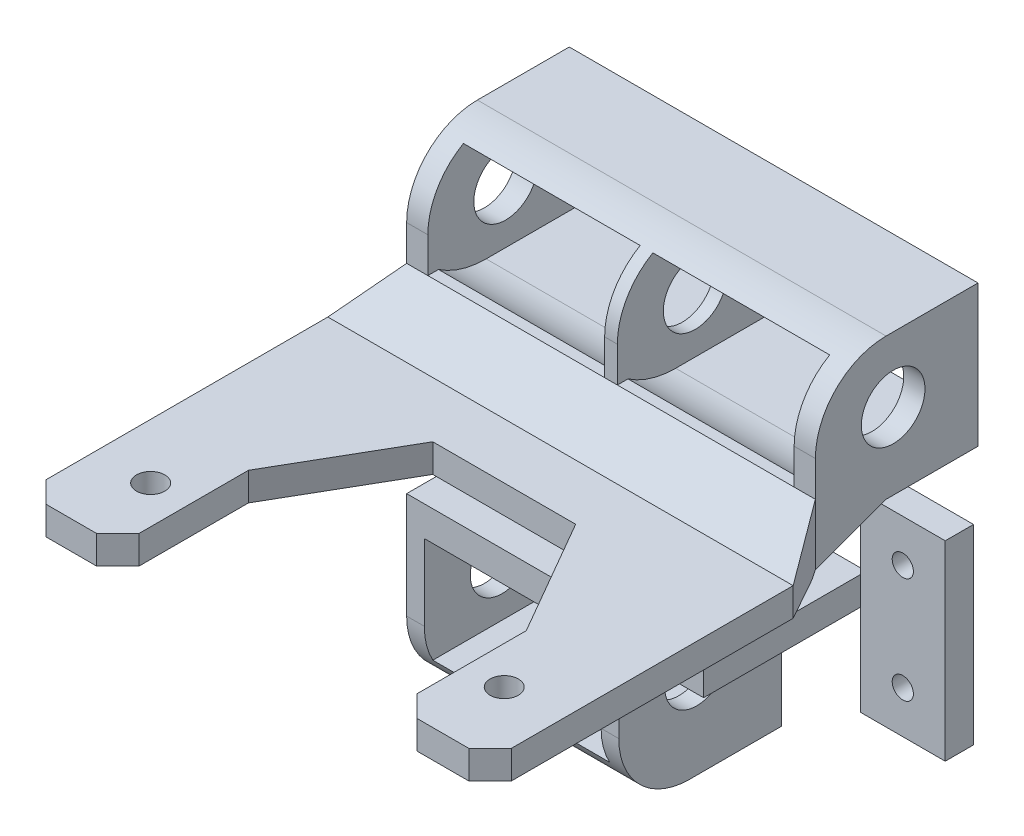
SolidWorks part; units mm, degrees
ref_plane "Alzado" through (0, 0, 0) normal (0, 0, 1) x (1, 0, 0)
ref_plane "Planta" through (0, 0, 0) normal (0, 1, 0) x (1, 0, 0)
ref_plane "Vista lateral" through (0, 0, 0) normal (1, 0, 0) x (0, 0, -1)
sketch "Croquis2" plane through (0, 0, 0) normal (0, 0, 1) x (1, 0, 0)
  line L0 (30, 41) -> (57.8, 41)
  line L1 (0, 0) -> (30, 0)
  line L2 (0, 0) -> (0, 66.2)
  line L3 (-22.2756, 55.1) -> (45.3117, 55.1) construction
  line L4 (30, 0) -> (30, 41)
  line L7 (0, 66.2) -> (57.8, 66.2)
  line L8 (57.8, 41) -> (57.8, 66.2)
  line L9 (-13, 9.1) -> (37, 9.1) construction
  dimension "D1" = 30
  dimension "D2" = 57.8
  dimension "D5" = 11.1
  dimension "D6" = 46
  dimension "D7" = 9.1
extrude "Saliente-Extruir3" add sketch "Croquis2" along normal blind 3
sketch "Croquis6" plane through (0, 0, 3) normal (0, 0, 1) x (1, 0, 0)
  line L0 (30, 0) -> (30, 41) construction
  line L1 (0, 0) -> (30, 0)
  line L2 (0, 0) -> (0, 20)
  line L3 (0, 20) -> (30, 20)
  line L4 (30, 0) -> (30, 20)
  line L5 (0, 66.2) -> (0, 0) construction
  line L6 (57.8, 41) -> (57.8, 66.2) construction
  line L7 (0, 66.2) -> (57.8, 66.2)
  line L8 (0, 66.2) -> (0, 46.2)
  line L9 (0, 46.2) -> (57.8, 46.2)
  line L10 (57.8, 66.2) -> (57.8, 46.2)
  dimension "D1" = 20
  dimension "D2" = 20
extrude "Saliente-Extruir4" add sketch "Croquis6" along normal blind 20
sketch "Croquis22" plane through (0, 0, 23) normal (0, 0, 1) x (1, 0, 0)
  line L1 (61.8, 42.2) -> (-4, 42.2)
  line L2 (61.8, 42.2) -> (61.8, 51.2)
  line L3 (61.8, 51.2) -> (-4, 51.2)
  line L4 (-4, 42.2) -> (-4, 51.2)
  line L6 (0, 46.2) -> (57.8, 46.2) construction
  line L7 (0, 66.2) -> (0, 46.2) construction
  line L8 (57.8, 46.2) -> (57.8, 66.2) construction
  dimension "D1" = 9
  dimension "D2" = 5
  dimension "D3" = 4
  dimension "D4" = 4
extrude "Saliente-Extruir9" add sketch "Croquis22" along normal blind 50 and the other way blind 10
sketch "Croquis9" plane through (57.8, 0, 0) normal (1, 0, 0) x (0, 0, -1)
  line L1 (0, 41) -> (0, 66.2) construction
  line L2 (-23, 0) -> (0, 0) construction
  line L3 (0, 0) -> (0, 41) construction
  circle A0 centre (-12, 57) radius 4.5
  circle A1 centre (-12, 11) radius 4.5
  dimension "D1" = 9
  dimension "D2" = 9
  dimension "D3" = 46
  dimension "D4" = 12
  dimension "D5" = 11
  dimension "D6" = 12
extrude "Cortar-Extruir1" cut sketch "Croquis9" against normal through all
sketch "Croquis17" plane through (0, 0, 23) normal (0, 0, 1) x (1, 0, 0)
  line L0 (30, 6.5) -> (30, 15.5) construction
  line L3 (30, 6.5) -> (30, 15.5) construction
  line L4 (2.5, 3.25) -> (27.5, 3.25)
  line L5 (2.5, 3.25) -> (2.5, 18.75)
  line L6 (2.5, 18.75) -> (27.5, 18.75)
  line L7 (27.5, 3.25) -> (27.5, 18.75)
  line L8 (2.5, 3.25) -> (27.5, 18.75) construction
  line L9 (2.5, 18.75) -> (27.5, 3.25) construction
  line L10 (30, 11) -> (0, 11) construction
  line L11 (0, 20) -> (0, 0) construction
  point P6 (15, 11)
  dimension "D1" = 15.5
  dimension "D2" = 25
extrude "Cortar-Extruir6" cut sketch "Croquis17" against normal up to surface (23 mm away) up to face at (29.2667, 35.7333, 0)
sketch "Croquis18" plane through (0, 0, 23) normal (0, 0, 1) x (1, 0, 0)
  line L0 (-13.9, 57) -> (43.9, 57) construction
  line L1 (0, 66.2) -> (0, 51.2) construction
  line L2 (57.8, 51.2) -> (57.8, 66.2) construction
  line L3 (0, 57) -> (57.8, 57) construction
  line L4 (3, 49.125) -> (28, 49.125)
  line L5 (3, 49.125) -> (3, 64.875)
  line L6 (3, 64.875) -> (28, 64.875)
  line L7 (28, 49.125) -> (28, 64.875)
  line L8 (3, 49.125) -> (28, 64.875) construction
  line L9 (3, 64.875) -> (28, 49.125) construction
  line L10 (54.8, 49.125) -> (29.8, 49.125)
  line L11 (54.8, 49.125) -> (54.8, 64.875)
  line L12 (54.8, 64.875) -> (29.8, 64.875)
  line L13 (29.8, 49.125) -> (29.8, 64.875)
  line L14 (54.8, 49.125) -> (29.8, 64.875) construction
  line L15 (54.8, 64.875) -> (29.8, 49.125) construction
  point P6 (15.5, 57)
  point P11 (42.3, 57)
  dimension "D1" = 15.75
  dimension "D2" = 25
  dimension "D3" = 3
  dimension "D4" = 3
extrude "Cortar-Extruir7" cut sketch "Croquis18" against normal up to surface (23 mm away) up to face at (15, 11, 0)
sketch "Croquis12" plane through (0, 20, 0) normal (0, 1, 0) x (1, 0, 0)
  line L1 (30, 0) -> (30, -3)
  line L2 (42, 0) -> (42, -23)
  line L3 (42, -23) -> (0, -23)
  line L4 (0, -3) -> (0, -23)
  line L5 (30, -23) -> (0, -23) construction
  line L6 (30, -23) -> (30, -3) construction
  line L8 (0, -23) -> (0, -3) construction
  line L9 (30, -3) -> (0, -3)
  line L10 (42, 0) -> (30, 0)
  line L11 (30, -23) -> (42, -23)
  line L12 (30, -3) -> (0, -3) construction
  circle A0 centre (36, -19) radius 1.5
  circle A1 centre (36, -4) radius 1.5
  dimension "D3" = 4
  dimension "D5" = 3
  dimension "D6" = 3
  dimension "D10" = 6
  dimension "D1" = 12
  dimension "D2" = 15
sketch "Croquis14" plane through (0, 66.2, 0) normal (0, 1, 0) x (1, 0, 0)
  line L1 (57.8, -23) -> (57.8, 0) construction
  line L2 (61.8, -73) -> (-4, -73) construction
  line L3 (9.1566, -54.5253) -> (9.1566, -73)
  line L4 (18.6964, -38.0018) -> (9.1566, -54.5253)
  line L8 (48.4434, -54.5253) -> (38.9036, -38.0018)
  line L9 (38.9036, -38.0018) -> (18.6964, -38.0018)
  line L10 (61.8, -73) -> (-4, -73) construction
  line L11 (9.1566, -73) -> (48.4434, -73)
  line L12 (48.4434, -73) -> (48.4434, -54.5253)
  line L14 (19.7861, -73.0018) -> (29.8898, -73.0018) [skipped]
  line L15 (13.6446, -64.2518) -> (16.6756, -69.5018) [skipped]
  line L16 (39.9524, -71.1852) -> (42.9835, -65.9352) [skipped]
  arc A0 (29.0535, -73) -> (28.5465, -73) centre (28.8, -55.5018) ccw construction
  circle A1 centre (3.8, -63) radius 2
  circle A2 centre (53.8, -63) radius 2
  dimension "D3" = 4
  dimension "D4" = 4
  dimension "D5" = 35
  dimension "D6" = 10
  dimension "D7" = 4
  dimension "D2" = 25
  dimension "D1" = 50
extrude "Cortar-Extruir4" cut sketch "Croquis14" against normal through all
sketch "Croquis16" plane through (30, 0, 0) normal (1, 0, 0) x (0, 0, -1)
  line L0 (-2.25, 36.0874) -> (-6, 36.0874)
  line L1 (-2.25, 40.0874) -> (-6, 40.0874)
  line L2 (-2.25, 40.0874) -> (-2.25, 38.0874)
  line L3 (-2.25, 38.0874) -> (-6, 38.0874)
  line L4 (-6, 40.0874) -> (-6, 38.0874)
  line L5 (-2.25, 36.0874) -> (-2.25, 34.0874)
  line L6 (-2.25, 34.0874) -> (-6, 34.0874)
  line L7 (-6, 36.0874) -> (-6, 34.0874)
  line L8 (-2.25, 32.0874) -> (-6, 32.0874)
  line L9 (-2.25, 32.0874) -> (-2.25, 30.0874)
  line L10 (-2.25, 30.0874) -> (-6, 30.0874)
  line L11 (-6, 32.0874) -> (-6, 30.0874)
  line L12 (-2.25, 28.0874) -> (-6, 28.0874)
  line L13 (-2.25, 28.0874) -> (-2.25, 26.0874)
  line L14 (-2.25, 26.0874) -> (-6, 26.0874)
  line L15 (-6, 28.0874) -> (-6, 26.0874)
  line L16 (-3, 20) -> (-3, 41) construction
  dimension "D1" = 2
  dimension "D2" = 2
  dimension "D3" = 2
  dimension "D4" = 2
  dimension "D5" = 2
  dimension "D6" = 2
  dimension "D7" = 2
  dimension "D8" = 0.75
extrude "Cortar-Extruir5" cut sketch "Croquis16" against normal through all
sketch "Croquis23" plane through (3, 0, 0) normal (1, 0, 0) x (0, 0, -1)
  line L0 (-23, 49.125) -> (-14.755, 49.125)
  line L1 (-23, 49.125) -> (-23, 51.2)
  line L2 (-23, 51.2) -> (-21.5, 51.2)
  arc A0 (-21.5, 51.2) -> (-14.755, 49.125) centre (-14.755, 61.125) ccw
  dimension "D1" = 12
  dimension "D2" = 1.5
extrude "Saliente-Extruir10" add sketch "Croquis23" along normal up to surface (51.8 mm away) up to face at (54.8, 55.84, 13.8)
sketch "Croquis24" plane through (0, 0, 3) normal (0, 0, 1) x (1, 0, 0)
  line L0 (0, 38.0874) -> (0, 36.0874) construction
  line L1 (0, 41) -> (-13.9, 41)
  line L2 (0, 41) -> (0, 46.2)
  line L3 (0, 46.2) -> (-13.9, 46.2)
  line L4 (-13.9, 41) -> (-13.9, 46.2)
  line L5 (30, 41) -> (57.8, 41)
  line L6 (30, 41) -> (30, 46.2)
  line L7 (30, 46.2) -> (57.8, 46.2)
  line L8 (57.8, 41) -> (57.8, 46.2)
  line L9 (30, 36.0874) -> (30, 38.0874) construction
extrude "Cortar-Extruir9" cut sketch "Croquis24" against normal through all
fillet "Redondeo1" radius 10 1 edges at (28.9, 66.2, 23)
sketch "Croquis28" plane through (30, 0, 0) normal (1, 0, 0) x (0, 0, -1)
  line L0 (-9, 46.2) -> (-3, 40.2)
  line L1 (-13, 46.2) -> (0, 46.2) construction
  line L2 (-3, 40.0874) -> (-3, 46.2) construction
  line L3 (-3, 40.2) -> (-3, 46.2)
  line L4 (-3, 46.2) -> (-9, 46.2)
  line L5 (-3, 26) -> (-6, 23)
  line L6 (-3, 20) -> (-3, 26.0874) construction
  line L8 (-6, 23) -> (-3, 23)
  line L9 (-3, 23) -> (-3, 26)
  dimension "D1" = 6
  dimension "D2" = 6
  dimension "D3" = 3
  dimension "D4" = 3
extrude "Saliente-Extruir12" add sketch "Croquis28" against normal up to surface (30 mm away) up to face at (0, 57, 7.5)
sketch "Croquis29" plane through (0, 0, 0) normal (0, -1, 0) x (1, 0, 0)
  line L4 (0, 0) -> (30, 0)
  line L5 (30, 0) -> (30, 23)
  line L6 (30, 23) -> (0, 23)
  line L7 (0, 23) -> (0, 0)
  line L8 (0, 0) -> (30, 0)
  line L9 (30, 0) -> (30, 23)
  line L10 (30, 23) -> (0, 23)
  line L11 (0, 23) -> (0, 0)
  dimension "D1" = 0
extrude "Saliente-Extruir13" add sketch "Croquis29" along normal blind 2
fillet "Redondeo2" radius 10 1 edges at (15, -2, 23)
sketch "Croquis31" plane through (61.8, 0, 0) normal (1, 0, 0) x (0, 0, -1)
  line L0 (-13, 42.2) -> (-73, 42.2) construction
  line L1 (-73, 42.2) -> (-73, 51.2) construction
  line L2 (-73, 46.2) -> (-30.1407, 46.2)
  line L3 (-30.1407, 46.2) -> (-23, 51.2)
  line L4 (-23, 51.2) -> (-73, 51.2)
  line L5 (-73, 51.2) -> (-73, 46.2)
  line L6 (-13, 46.2) -> (-23.9899, 42.2)
  line L7 (-23.9899, 42.2) -> (-13, 42.2)
  line L8 (-13, 42.2) -> (-13, 46.2)
  dimension "D1" = 4
  dimension "D2" = 35
  dimension "D3" = 20
extrude "Cortar-Extruir10" cut sketch "Croquis31" against normal through all
chamfer "Chaflán1" distance 3 angle 45 4 edges at (61.8, 44.2, 73) (-4, 44.2, 73) (48.4434, 44.2, 73) (9.1566, 44.2, 73)
sketch "Croquis32" plane through (0, 51.2, 0) normal (0, 1, 0) x (1, 0, 0)
  line L0 (0, -13) -> (-4, -13)
  line L1 (-4, -13) -> (-4, -30.1407)
  line L2 (-4, -30.1407) -> (0, -23)
  line L3 (0, -23) -> (0, -13)
  line L4 (57.8, -13) -> (61.8, -13)
  line L5 (61.8, -13) -> (61.8, -30.1407)
  line L6 (61.8, -30.1407) -> (57.8, -23)
  line L7 (57.8, -23) -> (57.8, -13)
extrude "Cortar-Extruir11" cut sketch "Croquis32" against normal through all
extrude "Saliente-Extruir14" add sketch "Croquis12" along normal blind 3 and the other way blind 1 contours L3 L4 L9 L1 L10 L2 | A1 | A0
sketch "Croquis33" plane through (0, 0, 0) normal (0, 0, 1) x (1, 0, 0)
  line L1 (45.1664, 9.308) -> (57.1664, 9.308)
  line L2 (45.1664, 9.308) -> (45.1664, 36.308)
  line L3 (45.1664, 36.308) -> (57.1664, 36.308)
  line L4 (57.1664, 9.308) -> (57.1664, 36.308)
  circle A0 centre (51.1664, 30.308) radius 1.5
  circle A1 centre (51.1664, 15.308) radius 1.5
  dimension "D1" = 3
  dimension "D2" = 3
  dimension "D4" = 15
  dimension "D5" = 6
  dimension "D6" = 6
  dimension "D7" = 6
  dimension "D3" = 12
extrude "Saliente-Extruir15" add sketch "Croquis33" along normal blind 4 separate body
